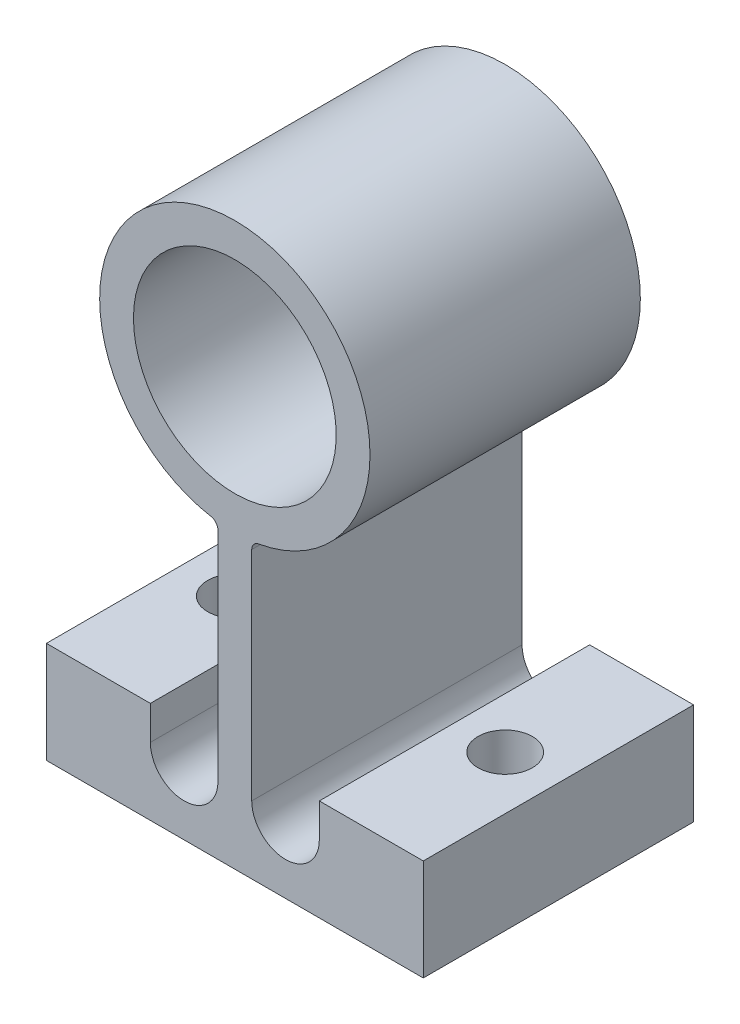
SolidWorks part; units mm, degrees
material "6061 Alloy"
ref_plane "Front Plane" through (0, 0, 0) normal (0, 0, 1) x (1, 0, 0)
ref_plane "Top Plane" through (0, 0, 0) normal (0, 1, 0) x (1, 0, 0)
ref_plane "Right Plane" through (0, 0, 0) normal (1, 0, 0) x (0, 0, -1)
sketch "Sketch1" plane through (0, 0, 0) normal (0, 0, -1) x (1, 0, 0)
  line L0 (0, 0) -> (0, 40.0837) construction
  line L1 (-17.706, 40.0837) -> (17.706, 40.0837)
  line L2 (17.706, 40.0837) -> (17.706, 30.5587)
  line L3 (17.706, 30.5587) -> (1.5875, 30.5587)
  line L4 (1.5875, 12.6004) -> (1.5875, 30.5587)
  line L5 (-1.5875, 12.6004) -> (-1.5875, 30.5587)
  line L6 (-17.706, 30.5587) -> (-1.5875, 30.5587)
  line L7 (-17.706, 40.0837) -> (-17.706, 30.5587)
  arc A0 (-1.5875, 12.6004) -> (1.5875, 12.6004) centre (0, 0) ccw
  circle A1 centre (0, 0) radius 9.525
  dimension "D2" = 25.4
  dimension "D3" = 19.05
  dimension "D1" = 40.0837
  dimension "D4" = 35.4119
  dimension "D5" = 3.175
  dimension "D6" = 9.525
extrude "Extrude1" add sketch "Sketch1" along normal mid plane 25.4
fillet "Bushing-side fillets" radius 0.7937 2 edges at (1.5875, -12.6004, 0) (-1.5875, -12.6004, 0)
fillet "Mount-side fillets" radius 0.7937 2 edges at (1.5875, -30.5587, 0) (-1.5875, -30.5587, 0)
hole_wizard "1/4 Mounting holes" positions "Sketch3" profile "Sketch2" tap size "1/4-20" standard "Ansi Inch"
sketch "Sketch3" plane through (0, -40.0837, 0) normal (0, -1, 0) x (1, 0, 0)
  line L0 (0, -12.7) -> (0, 12.7) construction
  line L1 (17.706, -12.7) -> (-17.706, -12.7) construction
  line L2 (17.706, 12.7) -> (-17.706, 12.7) construction
  point P0 (-12.7, 0)
  point P12 (12.7, 0)
  dimension "D1" = 25.4
sketch "Sketch2" plane through (-12.7, -40.0837, 0) normal (1, 0, 0) x (0, 0, -1)
  line L0 (0, 0) -> (0, 20.5838)
  line L1 (0, 20.5838) -> (2.5527, 19.05)
  line L2 (2.5527, 19.05) -> (2.5527, 0)
  line L5 (2.5527, 0) -> (0, 0)
  line L10 (0, 20.5838) -> (-2.5527, 19.05) construction
  line L11 (0, -6.35) -> (0, 107.95) construction
  dimension "Tap Drill Dia." = 5.1054
  dimension "Tap Drill Depth" = 19.05
  dimension "Drill Angle" = 118
cosmetic thread "Hole Thread1" parameters "D1"=12.7, "D2"=6.35
cosmetic thread "Hole Thread2" parameters "D1"=12.7, "D2"=6.35
sketch "Sketch4" plane through (0, 0, -12.7) normal (0, 0, -1) x (-1, 0, 0)
  line L0 (1.5875, -29.7649) -> (1.5875, -33.7337)
  line L1 (7.9375, -33.7337) -> (7.9375, -30.5587)
  line L2 (17.706, -30.5587) -> (2.3812, -30.5587) construction
  line L3 (7.9375, -30.5587) -> (2.3812, -30.5587)
  line L4 (-17.706, -40.0837) -> (17.706, -40.0837) construction
  line L5 (0, 0) -> (0, -40.0837) construction
  line L6 (-7.9375, -30.5587) -> (-2.3812, -30.5587)
  line L7 (-7.9375, -33.7337) -> (-7.9375, -30.5587)
  line L8 (-1.5875, -29.7649) -> (-1.5875, -33.7337)
  arc A0 (1.5875, -33.7337) -> (7.9375, -33.7337) centre (4.7625, -33.7337) ccw
  arc A1 (1.5875, -29.7649) -> (2.3812, -30.5587) centre (2.3812, -29.7649) ccw construction
  arc A2 (1.5875, -29.7649) -> (2.3812, -30.5587) centre (2.3812, -29.7649) ccw
  circle A3 centre (4.7625, -33.7337) radius 3.175 construction
  circle A4 centre (-4.7625, -33.7337) radius 3.175 construction
  arc A5 (-1.5875, -29.7649) -> (-2.3812, -30.5587) centre (-2.3812, -29.7649) cw
  arc A6 (-1.5875, -33.7337) -> (-7.9375, -33.7337) centre (-4.7625, -33.7337) cw
  point P11 (4.7625, -36.9087)
  point P24 (-4.7625, -36.9087)
  dimension "D1" = 6.35
  dimension "D2" = 3.175
extrude "Extrude2" cut sketch "Sketch4" against normal through all
